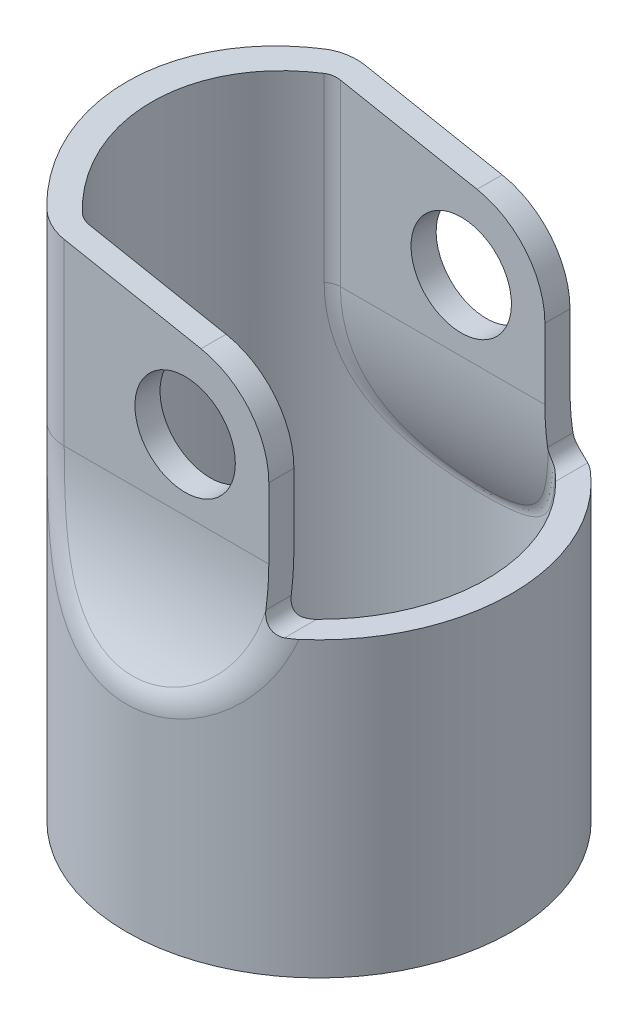
SolidWorks part; units mm, degrees
material "1060 合金"
ref_plane "前视基准面" through (0, 0, 0) normal (0, 0, 1) x (1, 0, 0)
ref_plane "上视基准面" through (0, 0, 0) normal (0, 1, 0) x (1, 0, 0)
ref_plane "右视基准面" through (0, 0, 0) normal (1, 0, 0) x (0, 0, -1)
sketch "草图1" plane through (0, 0, 0) normal (0, 1, 0) x (1, 0, 0)
  circle A0 centre (0, 0) radius 23
  dimension "D1" = 46
extrude "拉伸1" add sketch "草图1" along normal blind 65
sketch "草图2" plane through (0, 0, 0) normal (1, 0, 0) x (0, 0, -1)
  line L0 (-18, 65) -> (-18, 41.5831)
  line L1 (23, 65) -> (-23, 65) construction
  line L2 (-23, 65) -> (-23, 0) construction
  arc A0 (-18, 41.5831) -> (-23, 25) centre (-48, 41.5831) cw
  dimension "D3" = 30
  dimension "D1" = 40
  dimension "D2" = 18
extrude "拉伸2" cut sketch "草图2" against normal through all and the other way through all flip side to cut
mirror "镜向1" about plane through (0, 0, 0) normal (0, 0, 1) of "拉伸2"
fillet "圆角1" radius 5 6 edges at (-1.2246, 25.0493, -22.9674) (-1.2246, 25.0493, 22.9674) (-14.3178, 53.2916, -18) (14.3178, 53.2916, -18) (-14.3178, 53.2916, 18) (14.3178, 53.2916, 18)
shell "抽壳1" thickness 3 removed face at (0, 0, 23) removed face at (0, 65, 0)
sketch "草图3" plane through (0, 0, 18) normal (0, 0, 1) x (1, 0, 0)
  line L2 (12.4499, 65) -> (-12.4499, 65) construction
  circle A0 centre (2, 50) radius 6
  dimension "D3" = 12
  dimension "D1" = 2
  dimension "D2" = 15
extrude "拉伸3" cut sketch "草图3" against normal through all
sketch "草图4" plane through (0, 0, 18) normal (0, 0, 1) x (1, 0, 0)
  line L0 (3.8917, 59.8194) -> (-23, 65)
  line L1 (12, 50) -> (12, 37)
  line L2 (15.9082, 65) -> (12.4499, 65) construction
  line L3 (14, 35) -> (23, 35)
  line L4 (23, 0) -> (23, 65) construction
  arc A0 (12, 50) -> (3.8917, 59.8194) centre (2, 50) ccw
  arc A1 (12, 37) -> (14, 35) centre (14, 37) ccw
  point P14 (12, 35)
  dimension "D1" = 10
  dimension "D3" = 2
  dimension "D2" = 30
extrude "拉伸4" cut sketch "草图4" against normal through all and the other way through all
